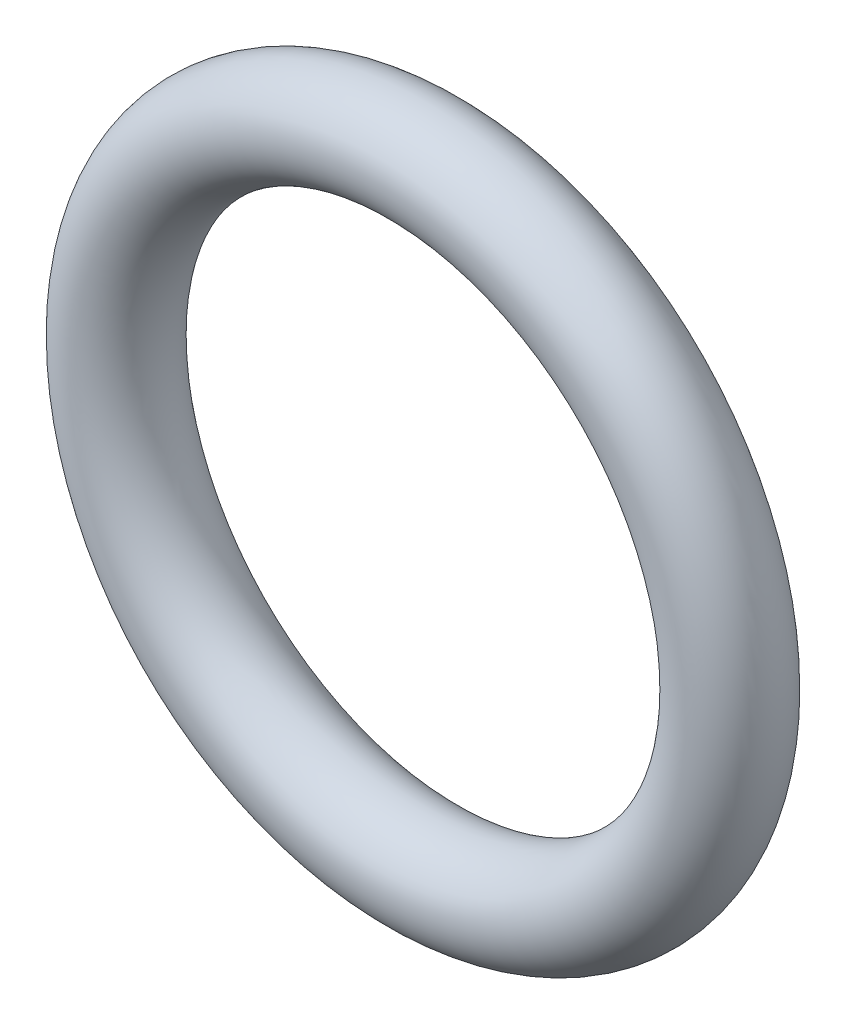
SolidWorks part; units mm, degrees
material "NBR"
ref_plane "Front" through (0, 0, 0) normal (0, 0, 1) x (1, 0, 0)
ref_plane "Top" through (0, 0, 0) normal (0, 1, 0) x (1, 0, 0)
ref_plane "Right" through (0, 0, 0) normal (1, 0, 0) x (0, 0, -1)
ref_axis "Axis1" through (0, 0, -0.9779) along (0, 0, 1)
sketch "Sketch1" plane through (0, 0, 0) normal (1, 0, 0) x (0, -1, 0)
  line L2 (-7.0409, 0) -> (7.0409, 0) construction
  line L3 (-4.6228, 0) -> (4.6228, 0) construction
  circle A0 centre (5.5118, 0) radius 0.889
  point P9 (4.6228, 0)
  dimension "Width" = 1.778
  dimension "ID" = 9.2456
revolve "Revolve1" add sketch "Sketch1" angle 360 about axis through (0, 0, -0.9779) along (0, 0, 1)
